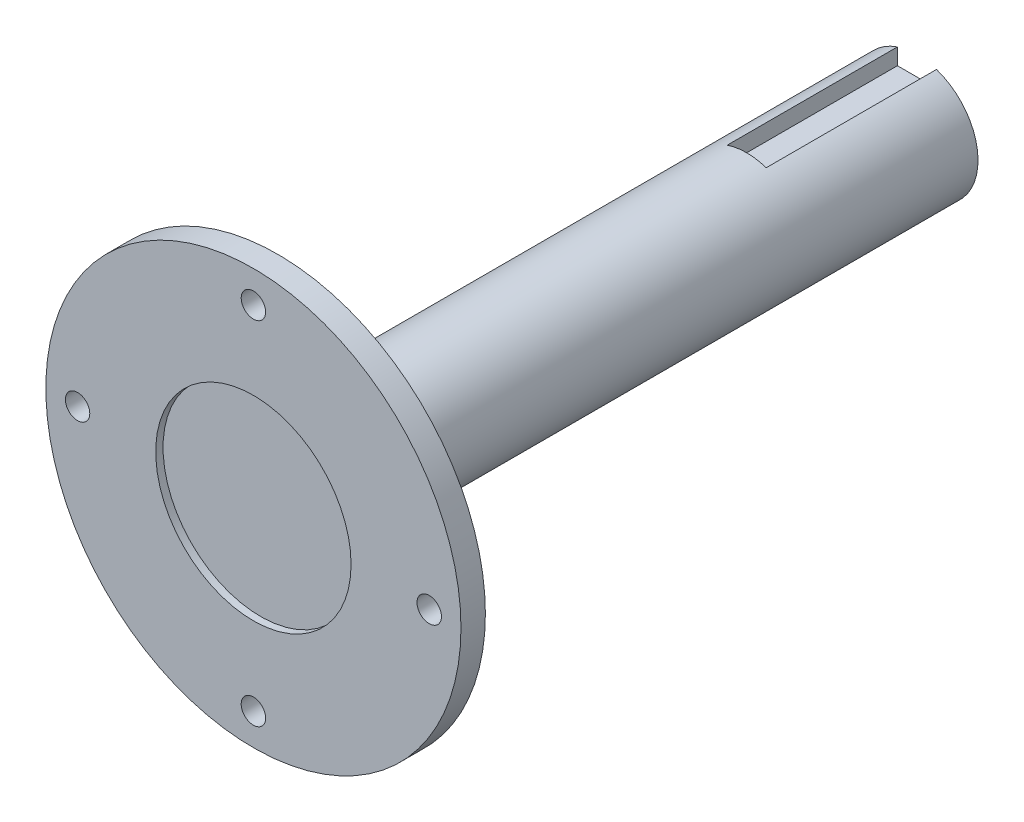
SolidWorks part; units mm, degrees
material "Plain Carbon Steel"
ref_plane "Front Plane" through (0, 0, 0) normal (0, 0, 1) x (1, 0, 0)
ref_plane "Top Plane" through (0, 0, 0) normal (0, 1, 0) x (1, 0, 0)
ref_plane "Right Plane" through (0, 0, 0) normal (1, 0, 0) x (0, 0, -1)
sketch "Sketch1" plane through (0, 0, 0) normal (0, 0, 1) x (1, 0, 0)
  circle A0 centre (0, 0) radius 12.5
  dimension "D1" = 25
extrude "Boss-Extrude1" add sketch "Sketch1" along normal blind 119.4
sketch "Sketch4" plane through (0, 0, 0) normal (0, 0, -1) x (-1, 0, 0)
  line L0 (0, 55) -> (0, -55) construction
  line L1 (-4, 8.5) -> (4, 8.5)
  line L2 (-4, 8.5) -> (-4, 16.5)
  line L3 (-4, 16.5) -> (4, 16.5)
  line L4 (4, 8.5) -> (4, 16.5)
  line L5 (-4, 8.5) -> (4, 16.5) construction
  line L6 (-4, 16.5) -> (4, 8.5) construction
  circle A0 centre (0, 0) radius 12.5 construction
  point P0 (0, 12.5)
  dimension "D1" = 8
  dimension "D2" = 8
extrude "Cut-Extrude1" cut sketch "Sketch4" against normal blind 35.4
sketch "Sketch5" plane through (0, 0, 119.4) normal (0, 0, 1) x (1, 0, 0)
  circle A0 centre (0, 0) radius 15.3
  dimension "D1" = 30.6
extrude "Boss-Extrude2" add sketch "Sketch5" along normal blind 2
sketch "Sketch10" plane through (0, 0, 121.4) normal (0, 0, 1) x (1, 0, 0)
  circle A0 centre (0, 0) radius 12.5
  dimension "D1" = 25
extrude "Boss-Extrude5" add sketch "Sketch10" along normal blind 15
sketch "Sketch14" plane through (0, 0, 0) normal (0, 0, -1) x (-1, 0, 0)
  circle A0 centre (0, 0) radius 12.5
  dimension "D1" = 25
extrude "Cut-Extrude3" cut sketch "Sketch14" against normal blind 0.5363
hole_wizard "M6x1.0 Tapped Hole2" positions "Sketch17" profile "Sketch18" tap size "M6x1.0" standard "ANSI Metric"
sketch "Sketch17" plane through (0, 0, 0.5363) normal (0, 0, -1) x (-1, 0, 0)
  point P0 (0, 0)
sketch "Sketch18" plane through (0, 0, 0.5363) normal (1, 0, 0) x (0, 1, 0)
  line L0 (0, 0) -> (0, 20)
  line L1 (0, 20) -> (2.5, 18.4978)
  line L2 (2.5, 18.4978) -> (2.5, 0)
  line L5 (2.5, 0) -> (0, 0)
  line L10 (0, 20) -> (-2.5, 18.4978) construction
  line L11 (0, -6.35) -> (0, 107.95) construction
  dimension "Tap Drill Dia." = 5
  dimension "Tap Drill Depth" = 20
  dimension "Drill Angle" = 118
cosmetic thread "Hole Thread4" parameters "D1"=5, "D2"=6
sketch "Sketch20" plane through (0, 0, 136.4) normal (0, 0, 1) x (1, 0, 0)
  circle A0 centre (0, 0) radius 42.5
  dimension "D1" = 85
extrude "Boss-Extrude6" add sketch "Sketch20" against normal blind 5
fillet "Fillet3" radius 10 1 edges at (12.5, 0, 131.4)
hole_wizard "M6x1.0 Tapped Hole3" positions "Sketch21" profile "Sketch22" tap size "M6x1.0" standard "ANSI Metric" end condition up to next
sketch "Sketch21" plane through (0, 0, 136.4) normal (0, 0, 1) x (1, 0, 0)
  line L0 (0, -46.75) -> (0, 46.75) construction
  line L1 (46.75, 0) -> (-46.75, 0) construction
  circle A0 centre (0, 0) radius 36
  point P0 (0, 36)
  point P4 (36, 0)
  point P8 (0, -36)
  point P10 (-36, 0)
  dimension "D1" = 72
sketch "Sketch22" plane through (0, 36, 136.4) normal (1, 0, 0) x (0, -1, 0)
  line L0 (0, 0) -> (0, 5)
  line L1 (0, 5) -> (2.5, 5)
  line L2 (2.5, 5) -> (2.5, 0)
  line L5 (2.5, 0) -> (0, 0)
  line L11 (0, -6.35) -> (0, 107.95) construction
  dimension "Thru Tap Drill Dia." = 5
  dimension "Thru Tap Drill Depth" = 5
cosmetic thread "Hole Thread5" parameters "D2"=6
cosmetic thread "Hole Thread6" parameters "D2"=6
cosmetic thread "Hole Thread7" parameters "D2"=6
cosmetic thread "Hole Thread8" parameters "D2"=6
sketch "Sketch23" plane through (0, 0, 136.4) normal (0, 0, 1) x (1, 0, 0)
  circle A0 centre (0, 0) radius 20
  dimension "D1" = 40
extrude "Cut-Extrude4" cut sketch "Sketch23" against normal blind 1.5
